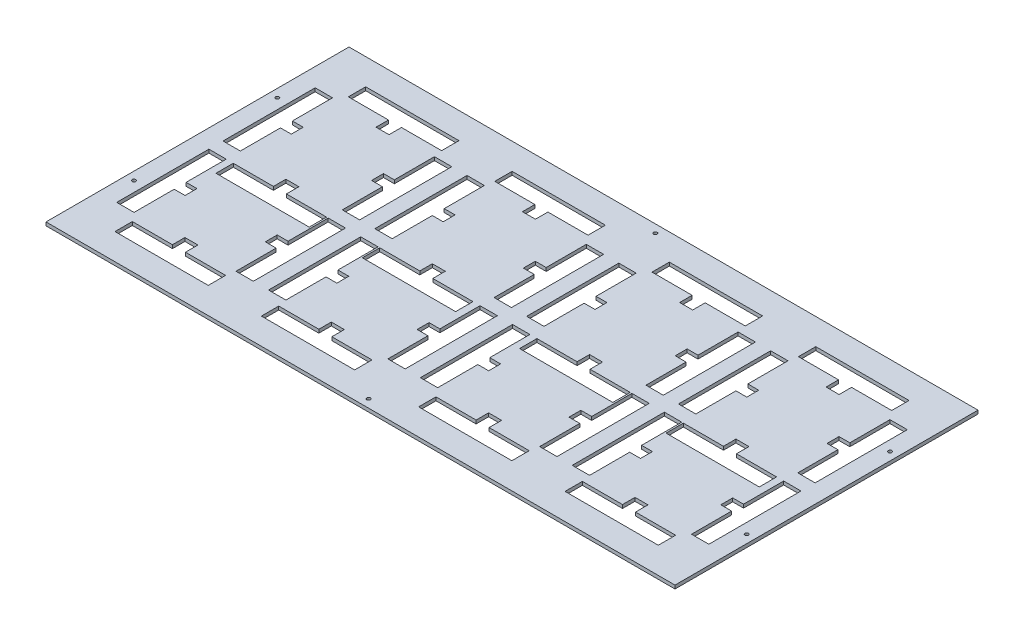
SolidWorks part; units mm, degrees
ref_plane "Front Plane" through (0, 0, 0) normal (0, 0, 1) x (1, 0, 0)
ref_plane "Top Plane" through (0, 0, 0) normal (0, 1, 0) x (1, 0, 0)
ref_plane "Right Plane" through (0, 0, 0) normal (1, 0, 0) x (0, 0, -1)
sketch "Sketch1" plane through (0, 0, 0) normal (0, 1, 0) x (1, 0, 0)
  line L0 (0, 139.7) -> (0, -139.7) construction
  line L1 (-290, 139.7) -> (290, 139.7)
  line L2 (-290, 139.7) -> (-290, -139.7)
  line L3 (-290, -139.7) -> (290, -139.7)
  line L4 (290, 139.7) -> (290, -139.7)
  line L5 (-290, 139.7) -> (290, -139.7) construction
  line L6 (-290, -139.7) -> (290, 139.7) construction
  line L7 (-282.5, 132.2) -> (282.5, 132.2) construction
  line L8 (-282.5, 132.2) -> (-282.5, -132.2) construction
  line L9 (-282.5, -132.2) -> (282.5, -132.2) construction
  line L10 (282.5, 132.2) -> (282.5, -132.2) construction
  line L11 (-282.5, 132.2) -> (282.5, -132.2) construction
  line L12 (-282.5, -132.2) -> (282.5, 132.2) construction
  line L13 (-290, 0) -> (290, 0) construction
  line L14 (282.5, 132.2) -> (282.5, -132.2) construction
  circle A0 centre (-282.5, 66.1) radius 1.65
  circle A3 centre (-282.5, -66.1) radius 1.65
  circle A10 centre (282.5, -66.1) radius 1.65
  circle A11 centre (282.5, 66.1) radius 1.65
  circle A12 centre (0, 132.2) radius 1.65
  circle A13 centre (0, -132.2) radius 1.65
  point P0 (0, 0)
  point P6 (0, 0)
  dimension "D5" = 3.3
  dimension "D12" = 3.3
  dimension "D13" = 3.3
  dimension "D1" = 580
  dimension "D2" = 279.4
  dimension "D3" = 7.5
  dimension "D4" = 7.5
  dimension "D8" = 66.1
extrude "Boss-Extrude1" add sketch "Sketch1" along normal blind 3.175
sketch "Sketch2" plane through (0, 3.175, 0) normal (0, 1, 0) x (1, 0, 0)
  line L0 (0, 139.7) -> (0, -139.7) construction
  line L1 (290, 139.7) -> (-290, 139.7) construction
  line L2 (-290, -139.7) -> (290, -139.7) construction
  line L3 (-190, 139.7) -> (-190, -139.7) construction
  line L4 (-252, 139.7) -> (-252, -139.7) construction
  line L5 (-290, 0) -> (290, 0) construction
  line L6 (-290, 139.7) -> (-290, -139.7) construction
  line L7 (290, -139.7) -> (290, 139.7) construction
  line L8 (-247, 54.5) -> (-257, 54.5)
  line L12 (-247, 54.5) -> (-247, 43.5)
  line L13 (-210, 139.7) -> (-210, -139.7) construction
  line L14 (-163, 43.5) -> (-163, 6.5)
  line L15 (-273, 91.5) -> (-257, 91.5)
  line L16 (-273, 91.5) -> (-273, 6.5)
  line L17 (-273, 6.5) -> (-257, 6.5)
  line L19 (-173, 43.5) -> (-163, 43.5)
  line L20 (-163, 54.5) -> (-163, 91.5)
  line L21 (-257, 54.5) -> (-257, 91.5)
  line L22 (-247, 43.5) -> (-257, 43.5)
  line L23 (-257, 43.5) -> (-257, 6.5)
  line L24 (-147, 6.5) -> (-163, 6.5)
  line L25 (-147, 91.5) -> (-147, 6.5)
  line L26 (-147, 91.5) -> (-163, 91.5)
  line L27 (-173, 54.5) -> (-173, 43.5)
  line L28 (-173, 54.5) -> (-163, 54.5)
  line L29 (-173, -54.5) -> (-163, -54.5)
  line L30 (-173, -54.5) -> (-173, -43.5)
  line L31 (-147, -91.5) -> (-163, -91.5)
  line L32 (-147, -91.5) -> (-147, -6.5)
  line L33 (-147, -6.5) -> (-163, -6.5)
  line L34 (-257, -43.5) -> (-257, -6.5)
  line L35 (-247, -43.5) -> (-257, -43.5)
  line L36 (-257, -54.5) -> (-257, -91.5)
  line L37 (-163, -54.5) -> (-163, -91.5)
  line L38 (-173, -43.5) -> (-163, -43.5)
  line L39 (-273, -6.5) -> (-257, -6.5)
  line L40 (-273, -91.5) -> (-273, -6.5)
  line L41 (-273, -91.5) -> (-257, -91.5)
  line L42 (-163, -43.5) -> (-163, -6.5)
  line L43 (-247, -54.5) -> (-247, -43.5)
  line L44 (-247, -54.5) -> (-257, -54.5)
  line L45 (-213.5, 5) -> (-201.5, 5)
  line L46 (-201.5, 5) -> (-201.5, -6.5)
  line L47 (-201.5, -6.5) -> (-164.5, -6.5)
  line L48 (-164.5, -6.5) -> (-164.5, -22.5)
  line L49 (-164.5, -22.5) -> (-250.5, -22.5)
  line L50 (-250.5, -22.5) -> (-250.5, -6.5)
  line L51 (-250.5, -6.5) -> (-213.5, -6.5)
  line L52 (-213.5, -6.5) -> (-213.5, 5)
  line L53 (-290, 46.55) -> (290, 46.55) construction
  line L54 (-213.5, 99.6) -> (-213.5, 88.1)
  line L55 (-250.5, 99.6) -> (-213.5, 99.6)
  line L56 (-250.5, 115.6) -> (-250.5, 99.6)
  line L57 (-164.5, 115.6) -> (-250.5, 115.6)
  line L58 (-164.5, 99.6) -> (-164.5, 115.6)
  line L59 (-201.5, 99.6) -> (-164.5, 99.6)
  line L60 (-201.5, 88.1) -> (-201.5, 99.6)
  line L61 (-213.5, 88.1) -> (-201.5, 88.1)
  line L62 (-213.5, -88.1) -> (-201.5, -88.1)
  line L63 (-201.5, -88.1) -> (-201.5, -99.6)
  line L64 (-201.5, -99.6) -> (-164.5, -99.6)
  line L65 (-164.5, -99.6) -> (-164.5, -115.6)
  line L66 (-164.5, -115.6) -> (-250.5, -115.6)
  line L67 (-250.5, -115.6) -> (-250.5, -99.6)
  line L68 (-250.5, -99.6) -> (-213.5, -99.6)
  line L69 (-213.5, -99.6) -> (-213.5, -88.1)
  line L70 (-140, 139.7) -> (-140, -139.7) construction
  line L71 (-66.5, -99.6) -> (-66.5, -88.1)
  line L72 (-29.5, -99.6) -> (-66.5, -99.6)
  line L73 (-29.5, -115.6) -> (-29.5, -99.6)
  line L74 (-115.5, -115.6) -> (-29.5, -115.6)
  line L75 (-115.5, -99.6) -> (-115.5, -115.6)
  line L76 (-78.5, -99.6) -> (-115.5, -99.6)
  line L77 (-78.5, -88.1) -> (-78.5, -99.6)
  line L78 (-66.5, -88.1) -> (-78.5, -88.1)
  line L79 (-66.5, 88.1) -> (-78.5, 88.1)
  line L80 (-78.5, 88.1) -> (-78.5, 99.6)
  line L81 (-78.5, 99.6) -> (-115.5, 99.6)
  line L82 (-115.5, 99.6) -> (-115.5, 115.6)
  line L83 (-115.5, 115.6) -> (-29.5, 115.6)
  line L84 (-29.5, 115.6) -> (-29.5, 99.6)
  line L85 (-29.5, 99.6) -> (-66.5, 99.6)
  line L86 (-66.5, 99.6) -> (-66.5, 88.1)
  line L87 (-66.5, -6.5) -> (-66.5, 5)
  line L88 (-29.5, -6.5) -> (-66.5, -6.5)
  line L89 (-29.5, -22.5) -> (-29.5, -6.5)
  line L90 (-115.5, -22.5) -> (-29.5, -22.5)
  line L91 (-115.5, -6.5) -> (-115.5, -22.5)
  line L92 (-78.5, -6.5) -> (-115.5, -6.5)
  line L93 (-78.5, 5) -> (-78.5, -6.5)
  line L94 (-66.5, 5) -> (-78.5, 5)
  line L95 (-33, -54.5) -> (-23, -54.5)
  line L96 (-33, -54.5) -> (-33, -43.5)
  line L97 (-117, -43.5) -> (-117, -6.5)
  line L98 (-7, -91.5) -> (-23, -91.5)
  line L99 (-7, -91.5) -> (-7, -6.5)
  line L100 (-7, -6.5) -> (-23, -6.5)
  line L101 (-107, -43.5) -> (-117, -43.5)
  line L102 (-117, -54.5) -> (-117, -91.5)
  line L103 (-23, -54.5) -> (-23, -91.5)
  line L104 (-33, -43.5) -> (-23, -43.5)
  line L105 (-23, -43.5) -> (-23, -6.5)
  line L106 (-133, -6.5) -> (-117, -6.5)
  line L107 (-133, -91.5) -> (-133, -6.5)
  line L108 (-133, -91.5) -> (-117, -91.5)
  line L109 (-107, -54.5) -> (-107, -43.5)
  line L110 (-107, -54.5) -> (-117, -54.5)
  line L111 (-107, 54.5) -> (-117, 54.5)
  line L112 (-107, 54.5) -> (-107, 43.5)
  line L113 (-133, 91.5) -> (-117, 91.5)
  line L114 (-133, 91.5) -> (-133, 6.5)
  line L115 (-133, 6.5) -> (-117, 6.5)
  line L116 (-23, 43.5) -> (-23, 6.5)
  line L117 (-33, 43.5) -> (-23, 43.5)
  line L118 (-23, 54.5) -> (-23, 91.5)
  line L119 (-117, 54.5) -> (-117, 91.5)
  line L120 (-107, 43.5) -> (-117, 43.5)
  line L121 (-7, 6.5) -> (-23, 6.5)
  line L122 (-7, 91.5) -> (-7, 6.5)
  line L123 (-7, 91.5) -> (-23, 91.5)
  line L124 (-117, 43.5) -> (-117, 6.5)
  line L125 (-33, 54.5) -> (-33, 43.5)
  line L126 (-33, 54.5) -> (-23, 54.5)
  line L127 (33, 54.5) -> (23, 54.5)
  line L128 (33, 54.5) -> (33, 43.5)
  line L129 (117, 43.5) -> (117, 6.5)
  line L130 (7, 91.5) -> (23, 91.5)
  line L131 (7, 91.5) -> (7, 6.5)
  line L132 (7, 6.5) -> (23, 6.5)
  line L133 (107, 43.5) -> (117, 43.5)
  line L134 (117, 54.5) -> (117, 91.5)
  line L135 (23, 54.5) -> (23, 91.5)
  line L136 (33, 43.5) -> (23, 43.5)
  line L137 (23, 43.5) -> (23, 6.5)
  line L138 (133, 6.5) -> (117, 6.5)
  line L139 (133, 91.5) -> (133, 6.5)
  line L140 (133, 91.5) -> (117, 91.5)
  line L141 (107, 54.5) -> (107, 43.5)
  line L142 (107, 54.5) -> (117, 54.5)
  line L143 (107, -54.5) -> (117, -54.5)
  line L144 (107, -54.5) -> (107, -43.5)
  line L145 (133, -91.5) -> (117, -91.5)
  line L146 (133, -91.5) -> (133, -6.5)
  line L147 (133, -6.5) -> (117, -6.5)
  line L148 (23, -43.5) -> (23, -6.5)
  line L149 (33, -43.5) -> (23, -43.5)
  line L150 (23, -54.5) -> (23, -91.5)
  line L151 (117, -54.5) -> (117, -91.5)
  line L152 (107, -43.5) -> (117, -43.5)
  line L153 (7, -6.5) -> (23, -6.5)
  line L154 (7, -91.5) -> (7, -6.5)
  line L155 (7, -91.5) -> (23, -91.5)
  line L156 (117, -43.5) -> (117, -6.5)
  line L157 (33, -54.5) -> (33, -43.5)
  line L158 (33, -54.5) -> (23, -54.5)
  line L159 (66.5, 5) -> (78.5, 5)
  line L160 (78.5, 5) -> (78.5, -6.5)
  line L161 (78.5, -6.5) -> (115.5, -6.5)
  line L162 (115.5, -6.5) -> (115.5, -22.5)
  line L163 (115.5, -22.5) -> (29.5, -22.5)
  line L164 (29.5, -22.5) -> (29.5, -6.5)
  line L165 (29.5, -6.5) -> (66.5, -6.5)
  line L166 (66.5, -6.5) -> (66.5, 5)
  line L167 (66.5, 99.6) -> (66.5, 88.1)
  line L168 (29.5, 99.6) -> (66.5, 99.6)
  line L169 (29.5, 115.6) -> (29.5, 99.6)
  line L170 (115.5, 115.6) -> (29.5, 115.6)
  line L171 (115.5, 99.6) -> (115.5, 115.6)
  line L172 (78.5, 99.6) -> (115.5, 99.6)
  line L173 (78.5, 88.1) -> (78.5, 99.6)
  line L174 (66.5, 88.1) -> (78.5, 88.1)
  line L175 (66.5, -88.1) -> (78.5, -88.1)
  line L176 (78.5, -88.1) -> (78.5, -99.6)
  line L177 (78.5, -99.6) -> (115.5, -99.6)
  line L178 (115.5, -99.6) -> (115.5, -115.6)
  line L179 (115.5, -115.6) -> (29.5, -115.6)
  line L180 (29.5, -115.6) -> (29.5, -99.6)
  line L181 (29.5, -99.6) -> (66.5, -99.6)
  line L182 (66.5, -99.6) -> (66.5, -88.1)
  line L183 (213.5, -99.6) -> (213.5, -88.1)
  line L184 (250.5, -99.6) -> (213.5, -99.6)
  line L185 (250.5, -115.6) -> (250.5, -99.6)
  line L186 (164.5, -115.6) -> (250.5, -115.6)
  line L187 (164.5, -99.6) -> (164.5, -115.6)
  line L188 (201.5, -99.6) -> (164.5, -99.6)
  line L189 (201.5, -88.1) -> (201.5, -99.6)
  line L190 (213.5, -88.1) -> (201.5, -88.1)
  line L191 (213.5, 88.1) -> (201.5, 88.1)
  line L192 (201.5, 88.1) -> (201.5, 99.6)
  line L193 (201.5, 99.6) -> (164.5, 99.6)
  line L194 (164.5, 99.6) -> (164.5, 115.6)
  line L195 (164.5, 115.6) -> (250.5, 115.6)
  line L196 (250.5, 115.6) -> (250.5, 99.6)
  line L197 (250.5, 99.6) -> (213.5, 99.6)
  line L198 (213.5, 99.6) -> (213.5, 88.1)
  line L199 (213.5, -6.5) -> (213.5, 5)
  line L200 (250.5, -6.5) -> (213.5, -6.5)
  line L201 (250.5, -22.5) -> (250.5, -6.5)
  line L202 (164.5, -22.5) -> (250.5, -22.5)
  line L203 (164.5, -6.5) -> (164.5, -22.5)
  line L204 (201.5, -6.5) -> (164.5, -6.5)
  line L205 (201.5, 5) -> (201.5, -6.5)
  line L206 (213.5, 5) -> (201.5, 5)
  line L207 (247, -54.5) -> (257, -54.5)
  line L208 (247, -54.5) -> (247, -43.5)
  line L209 (163, -43.5) -> (163, -6.5)
  line L210 (273, -91.5) -> (257, -91.5)
  line L211 (273, -91.5) -> (273, -6.5)
  line L212 (273, -6.5) -> (257, -6.5)
  line L213 (173, -43.5) -> (163, -43.5)
  line L214 (163, -54.5) -> (163, -91.5)
  line L215 (257, -54.5) -> (257, -91.5)
  line L216 (247, -43.5) -> (257, -43.5)
  line L217 (257, -43.5) -> (257, -6.5)
  line L218 (147, -6.5) -> (163, -6.5)
  line L219 (147, -91.5) -> (147, -6.5)
  line L220 (147, -91.5) -> (163, -91.5)
  line L221 (173, -54.5) -> (173, -43.5)
  line L222 (173, -54.5) -> (163, -54.5)
  line L223 (173, 54.5) -> (163, 54.5)
  line L224 (173, 54.5) -> (173, 43.5)
  line L225 (147, 91.5) -> (163, 91.5)
  line L226 (147, 91.5) -> (147, 6.5)
  line L227 (147, 6.5) -> (163, 6.5)
  line L228 (257, 43.5) -> (257, 6.5)
  line L229 (247, 43.5) -> (257, 43.5)
  line L230 (257, 54.5) -> (257, 91.5)
  line L231 (163, 54.5) -> (163, 91.5)
  line L232 (173, 43.5) -> (163, 43.5)
  line L233 (273, 6.5) -> (257, 6.5)
  line L234 (273, 91.5) -> (273, 6.5)
  line L235 (273, 91.5) -> (257, 91.5)
  line L236 (163, 43.5) -> (163, 6.5)
  line L237 (247, 54.5) -> (247, 43.5)
  line L238 (247, 54.5) -> (257, 54.5)
  point P16 (-247, 49)
  point P18 (-252, 54.5)
  point P36 (-173, 49)
  point P53 (-173, -49)
  point P54 (-247, -49)
  point P140 (-33, -49)
  point P141 (-107, -49)
  point P142 (-107, 49)
  point P143 (-33, 49)
  point P256 (33, 49)
  point P257 (107, 49)
  point P258 (107, -49)
  point P259 (33, -49)
  point P260 (247, -49)
  point P261 (173, -49)
  point P262 (173, 49)
  point P263 (247, 49)
  dimension "D1" = 190
  dimension "D2" = 62
  dimension "D4" = 85
  dimension "D5" = 11
  dimension "D6" = 49
  dimension "D7" = 16
  dimension "D8" = 5
  dimension "D3" = 42
  dimension "D9" = 5
  dimension "D10" = 46.55
  dimension "D11" = 50
  dimension "D12" = 12
  dimension "D13" = 8.5
extrude "Cut-Extrude1" cut sketch "Sketch2" against normal up to surface (3.175 mm away) up to face at (0, 0, 0)
equation "\"D12@Sketch1\"=\"D5@Sketch1\""
equation "\"D13@Sketch1\"=\"D5@Sketch1\""
equation "\"D9@Sketch2\"=\"D8@Sketch2\""
